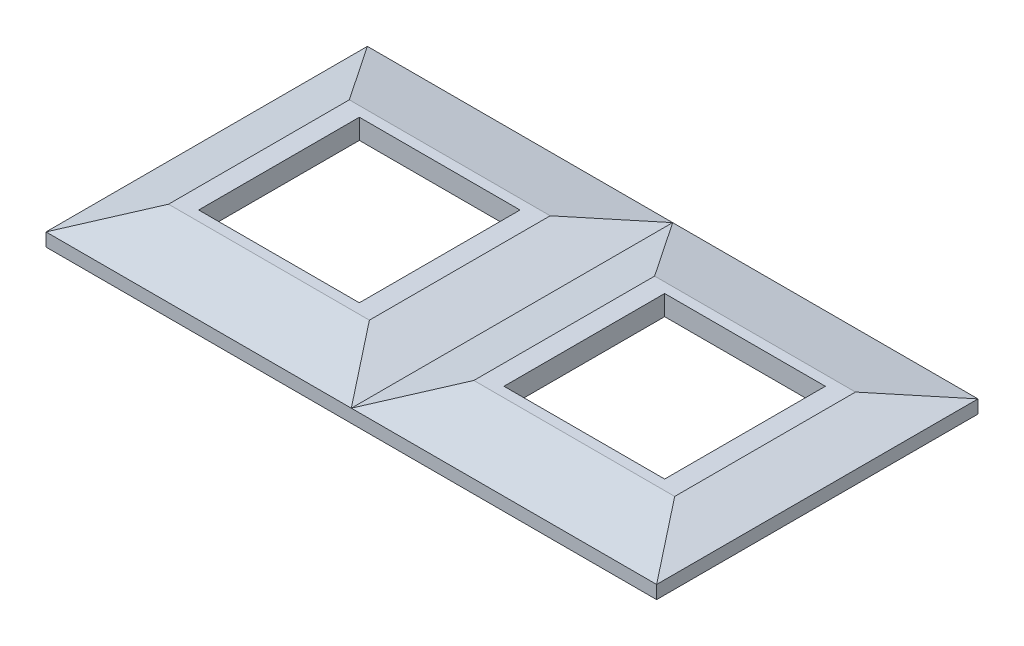
SolidWorks part; units mm, degrees
ref_plane "Спереди" through (0, 0, 0) normal (0, 0, 1) x (1, 0, 0)
ref_plane "Сверху" through (0, 0, 0) normal (0, 1, 0) x (1, 0, 0)
ref_plane "Справа" through (0, 0, 0) normal (1, 0, 0) x (0, 0, -1)
sketch "Эскиз1" plane through (0, 0, 0) normal (0, 0, 1) x (1, 0, 0)
  line L0 (0, 0) -> (-76, 0)
  line L1 (-76, 0) -> (-76, 3.2778)
  line L2 (-76, 3.2778) -> (-63, 7)
  line L3 (-63, 7) -> (-13, 7)
  line L4 (-38, 36.9052) -> (-38, -25.4966) construction
  line L5 (0, 3.2778) -> (-13, 7)
  line L6 (0, 40.9923) -> (0, -28.3407) construction
  line L7 (0, 3.2778) -> (13, 7)
  line L8 (0, 0) -> (76, 0)
  line L9 (63, 7) -> (13, 7)
  line L10 (76, 3.2778) -> (63, 7)
  line L11 (76, 0) -> (76, 3.2778)
  point P7 (-38, 0)
  point P8 (-38, 7)
  point P14 (38, 7)
  point P15 (38, 0)
extrude "Бобышка-Вытянуть1" add sketch "Эскиз1" along normal mid plane 80
sketch "Эскиз2" plane through (0, 0, 0) normal (1, 0, 0) x (0, 0, -1)
  line L0 (40, 0) -> (-40, 0)
  line L1 (-40, 3.2778) -> (-22.5, 7)
  line L2 (-40, 7) -> (40, 7) construction
  line L3 (-22.5, 7) -> (22.5, 7)
  line L5 (-40, 0) -> (-40, 3.2778)
  line L6 (0, 24.25) -> (0, -8.715) construction
  line L7 (40, 0) -> (40, 3.2778)
  line L8 (40, 3.2778) -> (22.5, 7)
  point P12 (0, 0)
  point P13 (0, 7)
  point P15 (0, 0)
  point P17 (0, 7)
extrude "Вырез-Вытянуть1" cut sketch "Эскиз2" against normal mid plane 156 flip side to cut
sketch "Эскиз3" plane through (0, 0, 0) normal (0, -1, 0) x (1, 0, 0)
  line L0 (0, 44.7636) -> (0, -49.792) construction
  line L1 (-58, 20) -> (-18, 20)
  line L2 (-58, 20) -> (-58, -20)
  line L3 (-58, -20) -> (-18, -20)
  line L4 (-18, 20) -> (-18, -20)
  line L5 (-58, 20) -> (-18, -20) construction
  line L6 (-58, -20) -> (-18, 20) construction
  line L7 (58, -20) -> (18, 20) construction
  line L8 (58, 20) -> (18, -20) construction
  line L9 (18, 20) -> (18, -20)
  line L10 (58, -20) -> (18, -20)
  line L11 (58, 20) -> (58, -20)
  line L12 (58, 20) -> (18, 20)
  point P0 (-38, 0)
  point P12 (38, 0)
extrude "Вырез-Вытянуть2" cut sketch "Эскиз3" against normal through all
sketch "Эскиз4" plane through (0, 0, 0) normal (0, -1, 0) x (1, 0, 0)
  line L0 (0, 52.3062) -> (0, -49.5733) construction
  line L1 (-73.5, 35.5) -> (-2.5, 35.5)
  line L2 (-73.5, 35.5) -> (-73.5, -35.5)
  line L3 (-73.5, -35.5) -> (-2.5, -35.5)
  line L4 (-2.5, 35.5) -> (-2.5, -35.5)
  line L5 (-73.5, 35.5) -> (-2.5, -35.5) construction
  line L6 (-73.5, -35.5) -> (-2.5, 35.5) construction
  line L7 (73.5, -35.5) -> (2.5, 35.5) construction
  line L8 (73.5, 35.5) -> (2.5, -35.5) construction
  line L9 (2.5, 35.5) -> (2.5, -35.5)
  line L10 (73.5, -35.5) -> (2.5, -35.5)
  line L11 (73.5, 35.5) -> (73.5, -35.5)
  line L12 (73.5, 35.5) -> (2.5, 35.5)
  point P0 (-38, 0)
  point P12 (38, 0)
  point P13 (0, 0)
extrude "Вырез-Вытянуть3" cut sketch "Эскиз4" against normal blind 2
